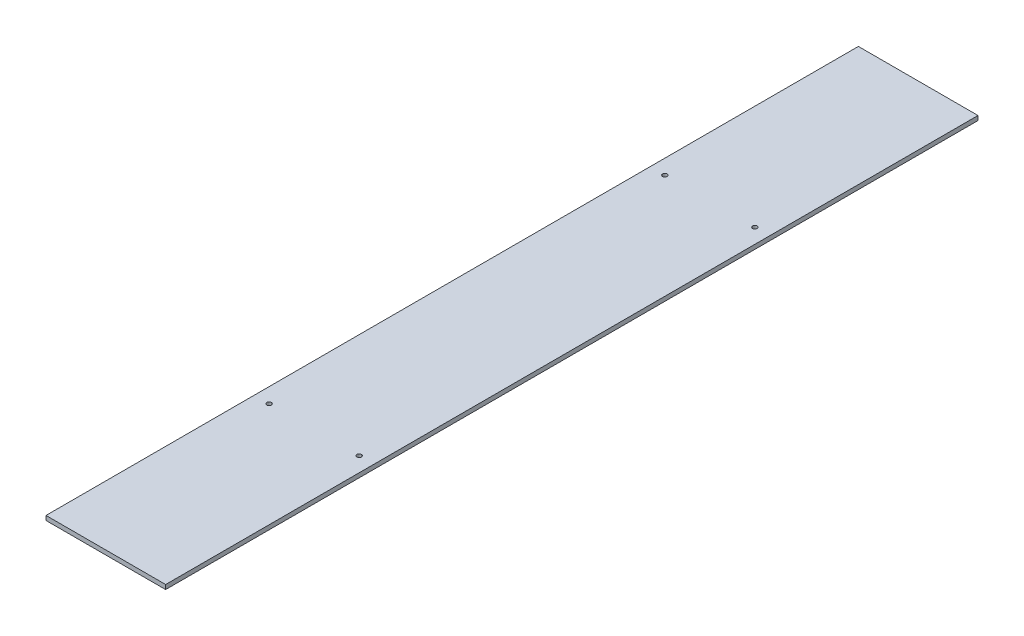
SolidWorks part; units mm, degrees
ref_plane "Front Plane" through (0, 0, 0) normal (0, 0, 1) x (1, 0, 0)
ref_plane "Top Plane" through (0, 0, 0) normal (0, 1, 0) x (1, 0, 0)
ref_plane "Right Plane" through (0, 0, 0) normal (1, 0, 0) x (0, 0, -1)
sketch "Sketch1" plane through (0, 0, 0) normal (0, 1, 0) x (1, 0, 0)
  line L0 (-43.175, 0) -> (43.175, 0) construction
  line L1 (-43.175, 293.175) -> (43.175, 293.175)
  line L2 (-43.175, 293.175) -> (-43.175, -293.175)
  line L3 (-43.175, -293.175) -> (43.175, -293.175)
  line L4 (43.175, 293.175) -> (43.175, -293.175)
  line L5 (-43.175, 293.175) -> (43.175, -293.175) construction
  line L6 (-43.175, -293.175) -> (43.175, 293.175) construction
  line L11 (0, 293.175) -> (0, -293.175) construction
  line L12 (-32.5, 285.675) -> (-32.5, 142.8375) construction
  line L13 (-32.5, 285.675) -> (32.5, 285.675) construction
  line L14 (-32.5, 285.675) -> (-32.5, -285.675) construction
  line L15 (-32.5, -285.675) -> (32.5, -285.675) construction
  line L16 (32.5, 285.675) -> (32.5, -285.675) construction
  line L17 (-32.5, 285.675) -> (32.5, -285.675) construction
  line L18 (-32.5, -285.675) -> (32.5, 285.675) construction
  line L19 (-32.5, 0) -> (-32.5, 142.8375) construction
  circle A3 centre (-32.5, 142.8375) radius 1.65
  circle A4 centre (32.5, 142.8375) radius 1.65
  circle A5 centre (32.5, -142.8375) radius 1.65
  circle A6 centre (-32.5, -142.8375) radius 1.65
  point P0 (0, 0)
  point P6 (0, 0)
  point P11 (0, 0)
  dimension "D5" = 3.3
  dimension "D1" = 10.675
  dimension "D2" = 7.5
  dimension "D3" = 86.35
  dimension "D4" = 586.35
extrude "Boss-Extrude1" add sketch "Sketch1" along normal blind 3.175
